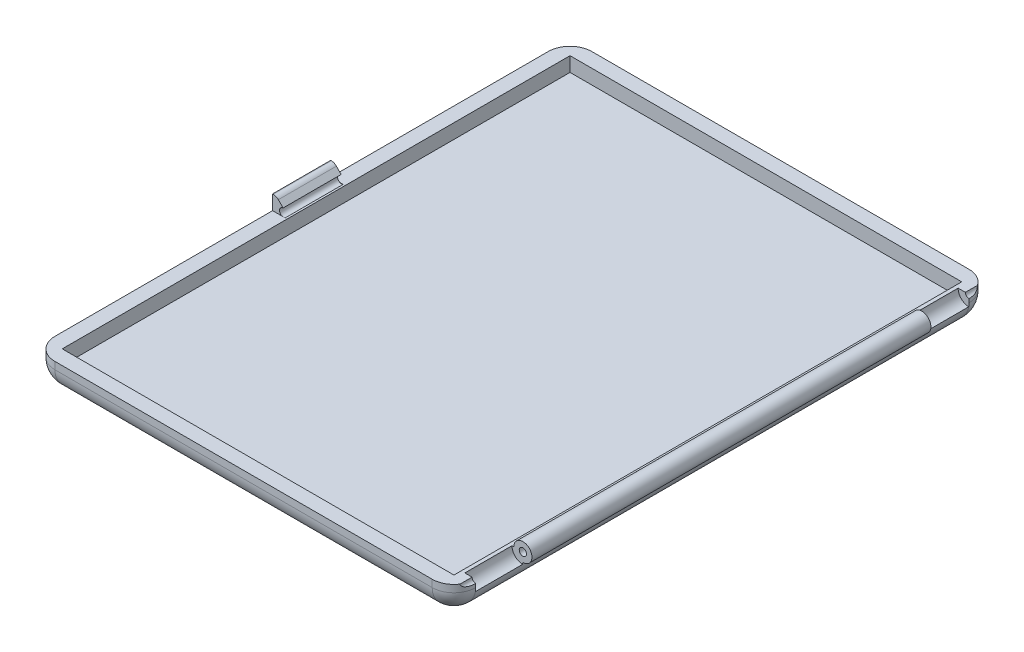
SolidWorks part; units mm, degrees
ref_plane "Front Plane" through (0, 0, 0) normal (0, 0, 1) x (1, 0, 0)
ref_plane "Top Plane" through (0, 0, 0) normal (0, 1, 0) x (1, 0, 0)
ref_plane "Right Plane" through (0, 0, 0) normal (1, 0, 0) x (0, 0, -1)
sketch "bottom" plane through (0, 0, 0) normal (0, 1, 0) x (1, 0, 0)
  line L0 (-2, 72) -> (56, 72)
  line L1 (0, 0) -> (54, 0)
  line L2 (0, 0) -> (0, 70)
  line L3 (0, 70) -> (54, 70)
  line L4 (54, 0) -> (54, 70)
  line L5 (56, -2) -> (56, 72)
  line L6 (-2, -2) -> (56, -2)
  line L7 (-2, -2) -> (-2, 72)
  dimension "D1" = 54
  dimension "D2" = 70
  dimension "D3" = 2
extrude "duvar" add sketch "bottom" along normal blind 4
extrude "taban" add sketch "bottom<2>" along normal blind 2 contours L1 L4 L3 L2 region at (27, 0, -35)
sketch "bottom<2>" plane through (0, 0, 0) normal (0, 1, 0) x (1, 0, 0) same geometry as "bottom"
fillet "Fillet2" radius 3 8 edges at (-2, 2, 2) (-2, 0, -35) (-2, 2, -72) (27, 0, -72) (56, 2, -72) (27, 0, 2) (56, 0, -35) (56, 2, 2)
ref_plane "mentese panel 1" through (0, 0, -1) normal (0, 0, 1) x (1, 0, 0)
ref_plane "mentese panel 2" through (0, 0, -69) normal (0, 0, -1) x (-1, 0, 0)
sketch "mentese out" plane through (0, 0, -69) normal (0, 0, -1) x (-1, 0, 0)
  circle A0 centre (-56, 4) radius 1.5
  dimension "D1" = 3
sketch "mentese in" plane through (0, 0, -1) normal (0, 0, 1) x (1, 0, 0)
  circle A0 centre (56, 4) radius 0.5
  dimension "D1" = 1
ref_plane "mentese panel 3" through (0, 0, -7.5) normal (0, 0, 1) x (1, 0, 0)
ref_plane "mentese panel 4" through (0, 0, -62.5) normal (0, 0, -1) x (-1, 0, 0)
sketch "centik" plane through (0, 4, 0) normal (0, 1, 0) x (1, 0, 0)
  line L0 (-2, 69) -> (-2, 1) construction
  line L1 (-2, 39) -> (-0.5, 39)
  line L2 (-2, 39) -> (-2, 31)
  line L3 (-2, 31) -> (-0.5, 31)
  line L4 (-0.5, 39) -> (-0.5, 31)
  point P7 (-2, 35)
  dimension "D1" = 8
  dimension "D2" = 1.5
  dimension "D3" = 4
extrude "centik cikinti" add sketch "centik" along normal blind 2
sketch "Sketch1" plane through (0, 0, -1) normal (0, 0, 1) x (1, 0, 0)
  circle A0 centre (56, 4) radius 1.5
extrude "Cut-Extrude1" cut sketch "Sketch1" against normal blind 6.5 contours A0
extrude "Cut-Extrude2" cut sketch "mentese out" against normal blind 6.5 contours A0
sketch "Sketch2" plane through (0, 0, -62.5) normal (0, 0, -1) x (-1, 0, 0)
  circle A0 centre (-56, 4) radius 1.25
  dimension "D1" = 2.5
extrude "Boss-Extrude3" add sketch "Sketch2" against normal up to vertex (55 mm away) up to point (54.5, 4, -7.5)
extrude "Cut-Extrude3" cut sketch "mentese in" against normal through all and the other way through all contours A0
chamfer "Chamfer1" distance 1 angle 45 1 edges at (-0.5, 6, -35)
fillet "Fillet3" radius 1 1 edges at (-1.5, 6, -35)
sketch "tirnak" plane through (0, 0, -31) normal (0, 0, 1) x (1, 0, 0)
  line L0 (-0.5, 5) -> (-0.5, 4) construction
  circle A0 centre (-0.5, 4.5) radius 0.55
  dimension "D1" = 1.1
extrude "tirnak ex" cut sketch "tirnak" against normal blind 8
